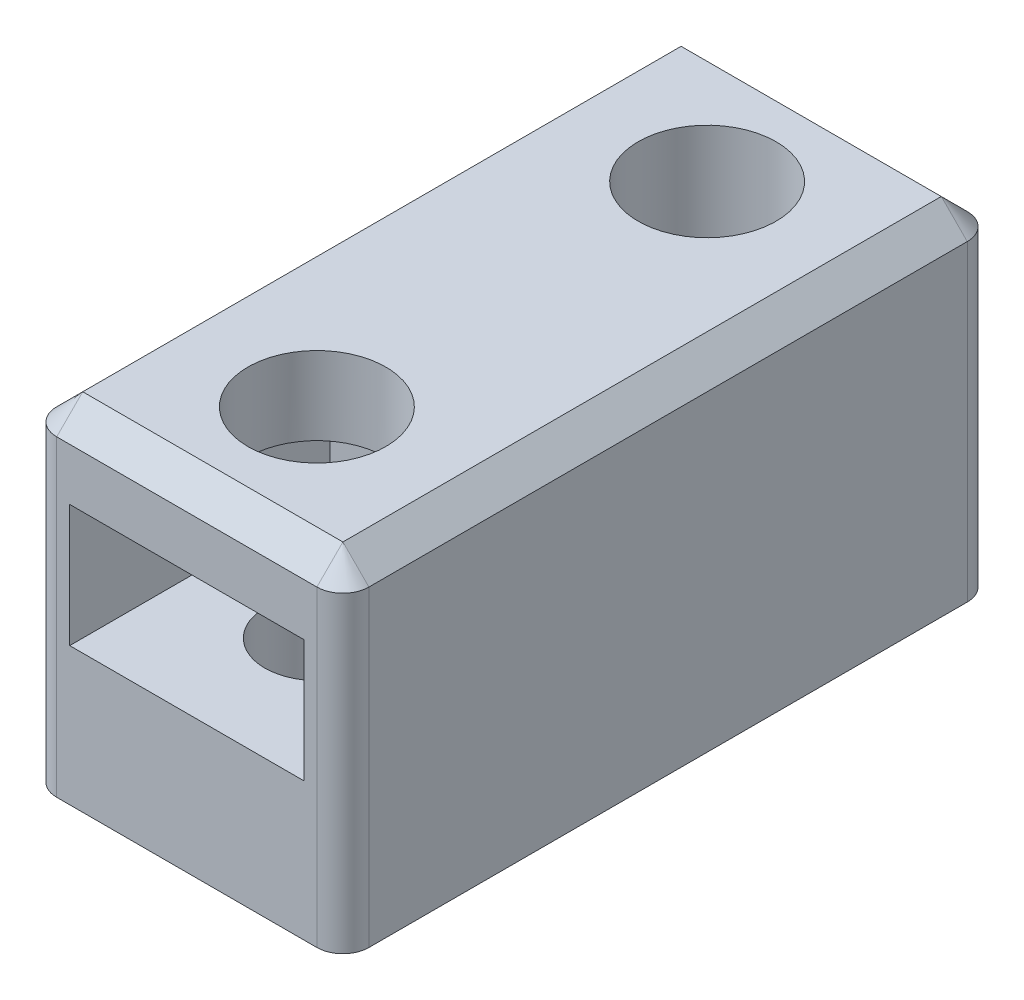
SolidWorks part; units mm, degrees
ref_plane "Front Plane" through (0, 0, 0) normal (0, 0, 1) x (1, 0, 0)
ref_plane "Top Plane" through (0, 0, 0) normal (0, 1, 0) x (1, 0, 0)
ref_plane "Right Plane" through (0, 0, 0) normal (1, 0, 0) x (0, 0, -1)
sketch "Sketch1" plane through (0, 0, 0) normal (0, 1, 0) x (1, 0, 0)
  line L0 (0, 7.5) -> (0, -7.5) construction
  line L1 (-6, 12.5) -> (6, 12.5)
  line L2 (-6, 12.5) -> (-6, -12.5)
  line L3 (-6, -12.5) -> (6, -12.5)
  line L4 (6, 12.5) -> (6, -12.5)
  line L5 (-6, 12.5) -> (6, -12.5) construction
  line L6 (-6, -12.5) -> (6, 12.5) construction
  circle A0 centre (0, 7.5) radius 2.65
  point P0 (0, 0)
  dimension "D2" = 5.3
  dimension "D3" = 15
  dimension "D1" = 25
  dimension "D4" = 12
extrude "Boss-Extrude1" add sketch "Sketch1" along normal mid plane 13
sketch "Sketch2" plane through (0, 0, 12.5) normal (0, 0, -1) x (-1, 0, 0)
  line L1 (-4.5, 3.5) -> (4.5, 3.5)
  line L2 (-4.5, 3.5) -> (-4.5, -1.2)
  line L3 (-4.5, -1.2) -> (4.5, -1.2)
  line L4 (4.5, 3.5) -> (4.5, -1.2)
  line L5 (-4.5, 3.5) -> (4.5, -1.2) construction
  line L6 (-4.5, -1.2) -> (4.5, 3.5) construction
  line L7 (-6, 6.5) -> (6, 6.5) construction
  point P0 (0, 1.15)
  point P6 (5.125, 2)
  point P7 (0, 0)
  point P11 (-4.254, 3)
  point P12 (0, 0)
  dimension "D1" = 4.7
  dimension "D2" = 9
  dimension "D3" = 3
extrude "Cut-Extrude1" cut sketch "Sketch2" along normal blind 10
sketch "Sketch3" plane through (0, 6.5, 0) normal (0, 1, 0) x (1, 0, 0)
  line L0 (0, 7.5) -> (0, -7.5) construction
  circle A0 centre (0, -7.5) radius 2.65
  dimension "D2" = 5.3
  dimension "D1" = 15
extrude "Cut-Extrude2" cut sketch "Sketch3" against normal up to surface (7.7 mm away) up to face at (0, -1.2, 7.5)
sketch "Sketch4" plane through (0, -6.5, 0) normal (0, -1, 0) x (1, 0, 0)
  line L0 (0, -7.5) -> (0, 7.5) construction
  circle A0 centre (0, 7.5) radius 2
  dimension "D2" = 4
  dimension "D1" = 15
extrude "Cut-Extrude3" cut sketch "Sketch4" against normal up to surface (5.3 mm away) up to face at (0, -1.2, 7.5)
fillet "Fillet1" radius 1 4 edges at (-6, 0, 12.5) (-6, 0, -12.5) (6, 0, -12.5) (6, 0, 12.5)
chamfer "Chamfer1" distance 1 angle 45 8 edges at (0, 6.5, -12.5) (-5.7071, 6.5, -12.2071) (5.7071, 6.5, -12.2071) (-6, 6.5, 0) (6, 6.5, 0) (-5.7071, 6.5, 12.2071) (5.7071, 6.5, 12.2071) (0, 6.5, 12.5)
